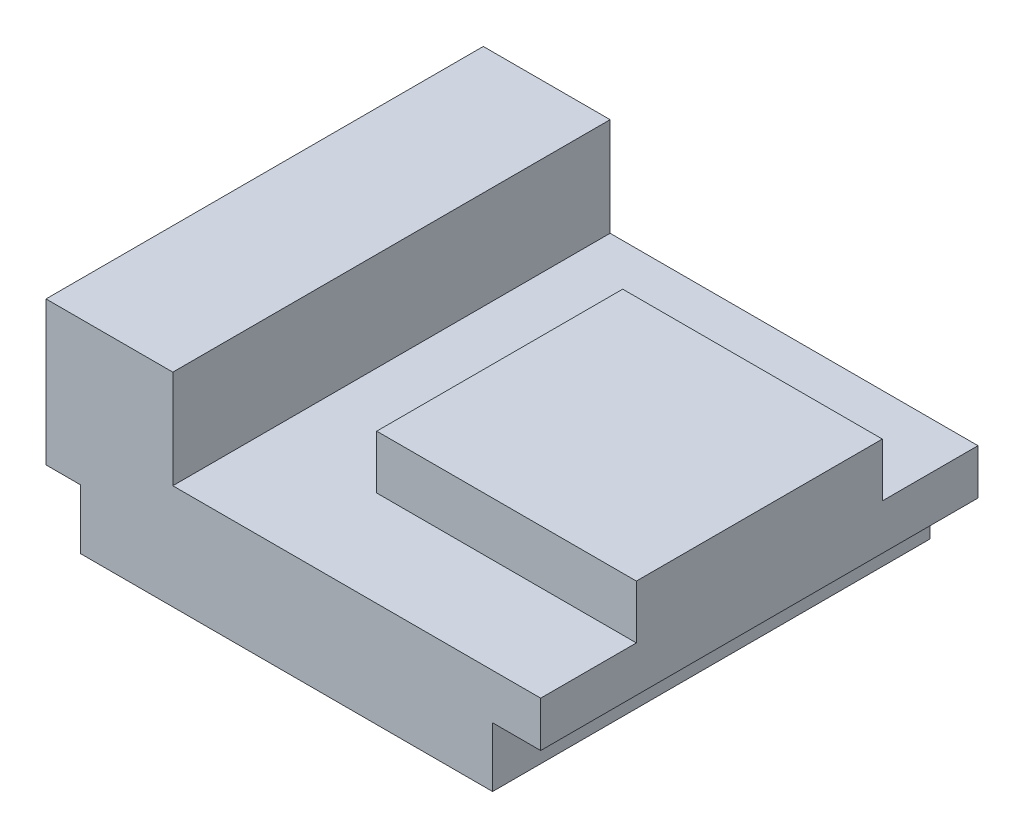
SolidWorks part; units mm, degrees
ref_plane "前视基准面" through (0, 0, 0) normal (0, 0, 1) x (1, 0, 0)
ref_plane "上视基准面" through (0, 0, 0) normal (0, 1, 0) x (1, 0, 0)
ref_plane "右视基准面" through (0, 0, 0) normal (1, 0, 0) x (0, 0, -1)
sketch "草图1" plane through (0, 0, 0) normal (0, 1, 0) x (1, 0, 0)
  line L1 (0, 0) -> (18.1, 0)
  line L2 (0, 0) -> (0, 16)
  line L3 (0, 16) -> (18.1, 16)
  line L4 (18.1, 0) -> (18.1, 16)
  dimension "D1" = 16
  dimension "D2" = 18.1
extrude "凸台-拉伸1" add sketch "草图1" along normal blind 1.66
sketch "草图2" plane through (0, 0, 0) normal (0, -1, 0) x (1, 0, 0)
  line L0 (0, 0) -> (18.1, 0) construction
  line L1 (1.26, 0) -> (16.34, 0)
  line L2 (1.26, 0) -> (1.26, -16)
  line L3 (1.26, -16) -> (16.34, -16)
  line L4 (16.34, 0) -> (16.34, -16)
  line L5 (18.1, -16) -> (0, -16) construction
  line L6 (0, -16) -> (0, 0) construction
  line L7 (18.1, 0) -> (18.1, -16) construction
  dimension "D1" = 1.26
  dimension "D2" = 1.76
extrude "凸台-拉伸2" add sketch "草图2" along normal blind 2.18
sketch "草图3" plane through (0, 1.66, 0) normal (0, 1, 0) x (1, 0, 0)
  line L0 (18.1, 0) -> (18.1, 16) construction
  line L1 (8.6, 12.5) -> (18.1, 12.5)
  line L2 (8.6, 12.5) -> (8.6, 3.5)
  line L3 (8.6, 3.5) -> (18.1, 3.5)
  line L4 (18.1, 12.5) -> (18.1, 3.5)
  line L5 (8.6, 12.5) -> (18.1, 3.5) construction
  line L6 (8.6, 3.5) -> (18.1, 12.5) construction
  line L7 (18.1, 8) -> (0, 8) construction
  line L8 (0, 16) -> (0, 0) construction
  point P0 (13.35, 8)
  dimension "D1" = 9
  dimension "D2" = 9.5
extrude "凸台-拉伸3" add sketch "草图3" along normal blind 1.96
sketch "草图4" plane through (0, 1.66, 0) normal (0, 1, 0) x (1, 0, 0)
  line L0 (0, 0) -> (18.1, 0) construction
  line L1 (0, 16) -> (4.64, 16)
  line L2 (0, 16) -> (0, 0)
  line L3 (0, 0) -> (4.64, 0)
  line L4 (4.64, 16) -> (4.64, 0)
  dimension "D1" = 4.64
extrude "凸台-拉伸4" add sketch "草图4" along normal blind 3.6
sketch "草图5" plane through (0, -2.18, 0) normal (0, -1, 0) x (1, 0, 0)
  line L0 (1.26, -8) -> (16.34, -8) construction
  line L1 (1.26, 0) -> (1.26, -16) construction
  line L2 (16.34, -16) -> (16.34, 0) construction
  circle A0 centre (8.26, -8) radius 1.5
  dimension "D1" = 7
  dimension "D2" = 3
extrude "凸台-拉伸5" add sketch "草图5" along normal blind 0.3
chamfer "倒角1" distance 0.3 angle 45 1 edges at (8.26, -2.18, -9.5)
